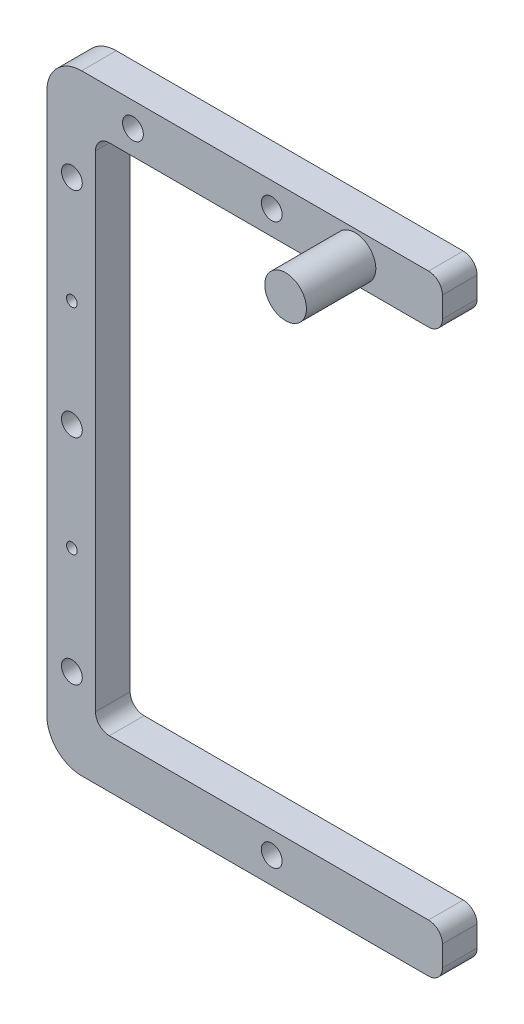
SolidWorks part; units mm, degrees
ref_plane "Front Plane" through (0, 0, 0) normal (0, 0, 1) x (1, 0, 0)
ref_plane "Top Plane" through (0, 0, 0) normal (0, 1, 0) x (1, 0, 0)
ref_plane "Right Plane" through (0, 0, 0) normal (1, 0, 0) x (0, 0, -1)
sketch "Sketch2" plane through (0, 0, 0) normal (0, 0, 1) x (1, 0, 0)
  line L0 (0, -35) -> (0, 35)
  line L1 (2, 37) -> (48, 37)
  line L2 (2, -37) -> (48, -37)
  line L3 (-2, -44) -> (48, -44)
  line L4 (-7, -39) -> (-7, 39)
  line L5 (-2, 44) -> (48, 44)
  line L6 (50, 42) -> (50, 39)
  line L7 (50, -42) -> (50, -39)
  line L8 (-7, -44) -> (50, -44) construction
  line L9 (-7, -44) -> (-7, 44) construction
  line L10 (-7, 44) -> (50, 44) construction
  line L11 (0, -37) -> (0, 37) construction
  line L12 (0, 37) -> (50, 37) construction
  line L13 (0, -37) -> (50, -37) construction
  arc A0 (-2, -44) -> (-7, -39) centre (-2, -39) cw
  arc A1 (-7, 39) -> (-2, 44) centre (-2, 39) cw
  arc A2 (0, 35) -> (2, 37) centre (2, 35) cw
  arc A3 (0, -35) -> (2, -37) centre (2, -35) ccw
  arc A4 (48, -44) -> (50, -42) centre (48, -42) ccw
  arc A5 (48, -37) -> (50, -39) centre (48, -39) cw
  arc A6 (48, 37) -> (50, 39) centre (48, 39) ccw
  arc A7 (48, 44) -> (50, 42) centre (48, 42) cw
  point P4 (0, 0)
  point P20 (0, 37)
  dimension "D4" = 5
  dimension "D5" = 2
  dimension "D1" = 70
  dimension "D3" = 7
extrude "Boss-Extrude1" add sketch "Sketch2" along normal blind 5
sketch "Sketch3" plane through (0, 0, 5) normal (0, 0, 1) x (1, 0, 0)
  line L0 (50, 40.5) -> (-10.6507, 40.5) construction
  line L1 (50, 39) -> (50, 42) construction
  line L2 (0, -35) -> (0, 35) construction
  circle A0 centre (37.4, 40.5) radius 3
  dimension "D2" = 6
  dimension "D1" = 37.4
extrude "Boss-Extrude2" add sketch "Sketch3" along normal blind 10
sketch "Sketch5" plane through (0, 0, 5) normal (0, 0, 1) x (1, 0, 0)
  line L0 (37.4, 40.5) -> (37.4, 28.833) construction
  line L1 (37.4, 40.5) -> (-21.2242, 40.5) construction
  line L2 (-3.4, 30) -> (-3.4, -35.8617) construction
  line L3 (25.4, 40.5) -> (25.4, -51.0254) construction
  circle A0 centre (25.4, 40.5) radius 1.5
  circle A1 centre (5.4, 40.5) radius 1.5
  circle A2 centre (-3.4, 30) radius 1.5
  circle A3 centre (-3.4, -0.85) radius 1.5
  circle A4 centre (-3.4, -31.7) radius 1.5
  circle A5 centre (25.4, -40.2) radius 1.5
  dimension "D1" = 3
  dimension "D2" = 3
  dimension "D7" = 3
  dimension "D8" = 3
  dimension "D9" = 3
  dimension "D12" = 3
  dimension "D3" = 12
  dimension "D4" = 20
  dimension "D5" = 8.8
  dimension "D6" = 10.5
  dimension "D10" = 30.85
  dimension "D11" = 30.85
  dimension "D13" = 8.5
extrude "Cut-Extrude1" cut sketch "Sketch5" against normal through all
sketch "Sketch6" plane through (0, 0, 5) normal (0, 0, 1) x (1, 0, 0)
  line L0 (-3.4, 30) -> (-3.4, -36.7709) construction
  line L1 (-3.4, -0.85) -> (6.201, -0.85) construction
  line L2 (-3.4, -31.7) -> (13.4163, -31.7) construction
  circle A0 centre (-3.4, 14.575) radius 0.77
  circle A1 centre (-3.4, -16.275) radius 0.77
  dimension "D3" = 1.54
  dimension "D4" = 1.54
  dimension "D1" = 15.425
  dimension "D2" = 15.425
extrude "Cut-Extrude2" cut sketch "Sketch6" against normal blind 3
cosmetic thread "Cosmetic Thread1" parameters "D2"=2
cosmetic thread "Cosmetic Thread2" parameters "D2"=2
equation "\"38.5mmmm\"=27.8036"
